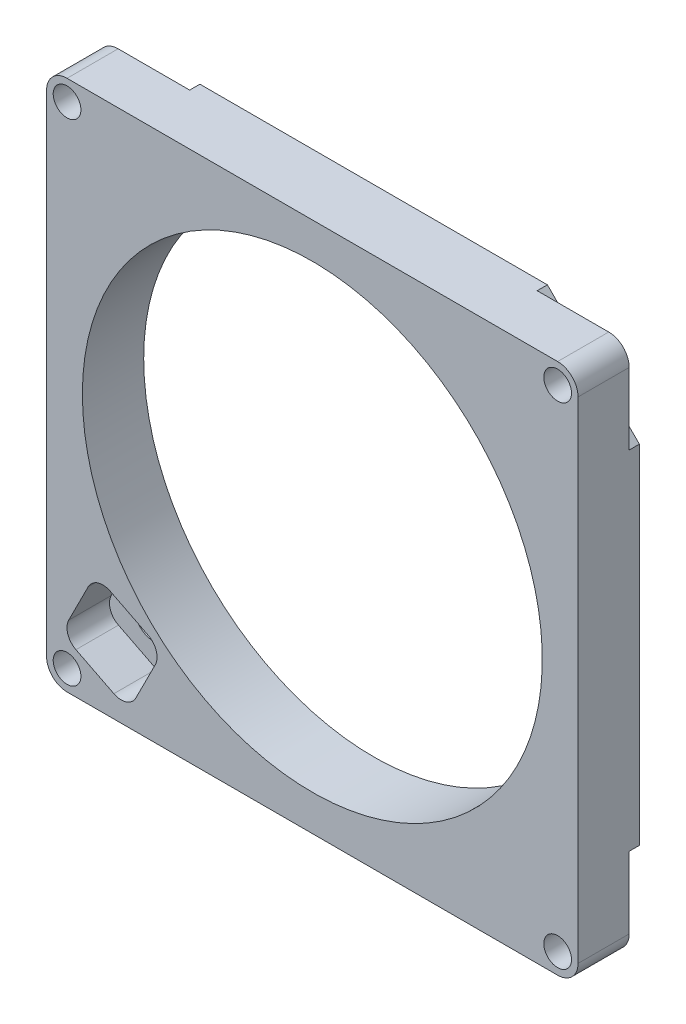
SolidWorks part; units mm, degrees
material "PET"
ref_plane "Front Plane" through (0, 0, 0) normal (0, 0, 1) x (1, 0, 0)
ref_plane "Top Plane" through (0, 0, 0) normal (0, 1, 0) x (1, 0, 0)
ref_plane "Right Plane" through (0, 0, 0) normal (1, 0, 0) x (0, 0, -1)
sketch "Sketch1" plane through (0, 0, 0) normal (0, 0, 1) x (1, 0, 0)
  line L8 (-213.995, 2363.8407) -> (-213.995, 2440.0407)
  line L9 (-217.17, 2443.2157) -> (-293.37, 2443.2157)
  line L10 (-296.545, 2440.0407) -> (-296.545, 2363.8407)
  line L11 (-293.37, 2360.6657) -> (-217.17, 2360.6657)
  arc A8 (-217.17, 2360.6657) -> (-213.995, 2363.8407) centre (-217.17, 2363.8407) ccw
  arc A9 (-213.995, 2440.0407) -> (-217.17, 2443.2157) centre (-217.17, 2440.0407) ccw
  arc A10 (-293.37, 2443.2157) -> (-296.545, 2440.0407) centre (-293.37, 2440.0407) ccw
  arc A11 (-296.545, 2363.8407) -> (-293.37, 2360.6657) centre (-293.37, 2363.8407) ccw
extrude "Boss-Extrude1" add sketch "Sketch1" against normal up to surface (7.9375 mm away)
sketch "Sketch2" plane through (0, 0, -7.9375) normal (0, 0, -1) x (-1, 0, 0)
  line L16 (282.2575, 2360.6657) -> (296.545, 2374.9532)
  line L17 (296.545, 2374.9532) -> (296.545, 2428.9282)
  line L18 (296.545, 2428.9282) -> (282.2575, 2443.2157)
  line L19 (282.2575, 2443.2157) -> (228.2825, 2443.2157)
  line L20 (228.2825, 2443.2157) -> (213.995, 2428.9282)
  line L21 (213.995, 2428.9282) -> (213.995, 2374.9532)
  line L22 (213.995, 2374.9532) -> (228.2825, 2360.6657)
  line L23 (228.2825, 2360.6657) -> (282.2575, 2360.6657)
  circle A1 centre (255.27, 2401.9407) radius 35.7188
extrude "Boss-Extrude2" add sketch "Sketch2" along normal blind 1.5875
sketch "Sketch3" plane through (0, 0, -7.9375) normal (0, 0, -1) x (-1, 0, 0)
  circle A1 centre (255.27, 2401.9407) radius 35.7188
  circle A2 centre (255.27, 2401.9407) radius 35.7188
  dimension "D1" = 0
extrude "Cut-Extrude1" cut sketch "Sketch3" against normal through all and the other way through all
hole_wizard "#6 Clearance Hole1" positions "Sketch5" profile "Sketch4" hole size "#6" standard "ANSI Inch" end condition through all
sketch "Sketch5" plane through (0, 0, -7.9375) normal (0, 0, -1) x (-1, 0, 0)
  point P0 (217.17, 2440.0407)
  point P2 (293.37, 2440.0407)
  point P4 (293.37, 2363.8407)
  point P6 (217.17, 2363.8407)
sketch "Sketch4" plane through (-217.17, 2440.0407, -7.9375) normal (1, 0, 0) x (0, 1, 0)
  line L0 (0, 0) -> (0, 7.9375)
  line L1 (0, 7.9375) -> (2.1526, 7.9375)
  line L2 (2.1526, 7.9375) -> (2.1526, 0)
  line L5 (2.1526, 0) -> (0, 0)
  line L11 (0, -6.35) -> (0, 107.95) construction
  dimension "Thru Hole Dia." = 4.3053
  dimension "Thru Hole Depth" = 7.9375
sketch "Sketch6" plane through (0, 0, 0) normal (0, 0, 1) x (1, 0, 0)
  line L0 (-286.0983, 2364.0731) -> (-291.989, 2367.0475)
  line L1 (-282.6861, 2365.1956) -> (-279.6585, 2371.1918)
  line L2 (-293.1115, 2370.4597) -> (-290.0839, 2376.4558)
  line L3 (-280.781, 2374.604) -> (-286.6717, 2377.5783)
  line L4 (-283.831, 2362.9283) -> (-288.939, 2378.7232) construction
  line L5 (-294.2563, 2368.1923) -> (-278.5137, 2373.4591) construction
  line L6 (-286.385, 2370.8257) -> (-291.5977, 2373.4577) construction
  arc A0 (-279.6585, 2371.1918) -> (-280.781, 2374.604) centre (-281.9259, 2372.3366) ccw
  arc A1 (-282.6861, 2365.1956) -> (-286.0983, 2364.0731) centre (-284.9535, 2366.3405) cw
  arc A2 (-290.0839, 2376.4558) -> (-286.6717, 2377.5783) centre (-287.8165, 2375.311) cw
  arc A3 (-291.989, 2367.0475) -> (-293.1115, 2370.4597) centre (-290.8441, 2369.3148) cw
  point P0 (-291.5977, 2373.4577)
  point P2 (-286.385, 2370.8257)
  point P4 (0, 0)
  dimension "D1" = 2.54
extrude "Cut-Extrude2" cut sketch "Sketch6" against normal offset from surface (6.604 mm away) 2.921 up to face at (-255.27, 2401.9407, -9.525)
hole_wizard "F (0.257) Diameter Hole1" positions "Sketch8" profile "Sketch7" hole size "F" standard "ANSI Inch" end condition through all
sketch "Sketch8" plane through (0, 0, -9.525) normal (0, 0, -1) x (-1, 0, 0)
  point P0 (286.385, 2370.8257)
sketch "Sketch7" plane through (-286.385, 2370.8257, -9.525) normal (1, 0, 0) x (0, 1, 0)
  line L0 (0, 0) -> (0, 9.525)
  line L1 (0, 9.525) -> (3.2639, 9.525)
  line L2 (3.2639, 9.525) -> (3.2639, 0)
  line L5 (3.2639, 0) -> (0, 0)
  line L11 (0, -6.35) -> (0, 107.95) construction
  dimension "Thru Hole Dia." = 6.5278
  dimension "Thru Hole Depth" = 9.525
hole_wizard "#51 (0.067) Diameter Hole1" positions "Sketch9" profile "Sketch10" hole size "#51" standard "ANSI Inch" end condition through all
sketch "Sketch9" plane through (0, 0, -9.525) normal (0, 0, -1) x (-1, 0, 0)
  point P0 (290.6199, 2373.0045)
  point P3 (290.5908, 2373.061)
  point P4 (290.6577, 2372.931)
  point P5 (290.5908, 2373.061)
sketch "Sketch10" plane through (-290.6199, 2373.0045, -9.525) normal (1, 0, 0) x (0, 1, 0)
  line L0 (0, 0) -> (0, 9.525)
  line L1 (0, 9.525) -> (0.8509, 9.525)
  line L2 (0.8509, 9.525) -> (0.8509, 0)
  line L5 (0.8509, 0) -> (0, 0)
  line L11 (0, -6.35) -> (0, 107.95) construction
  dimension "Thru Hole Dia." = 1.7018
  dimension "Thru Hole Depth" = 9.525
